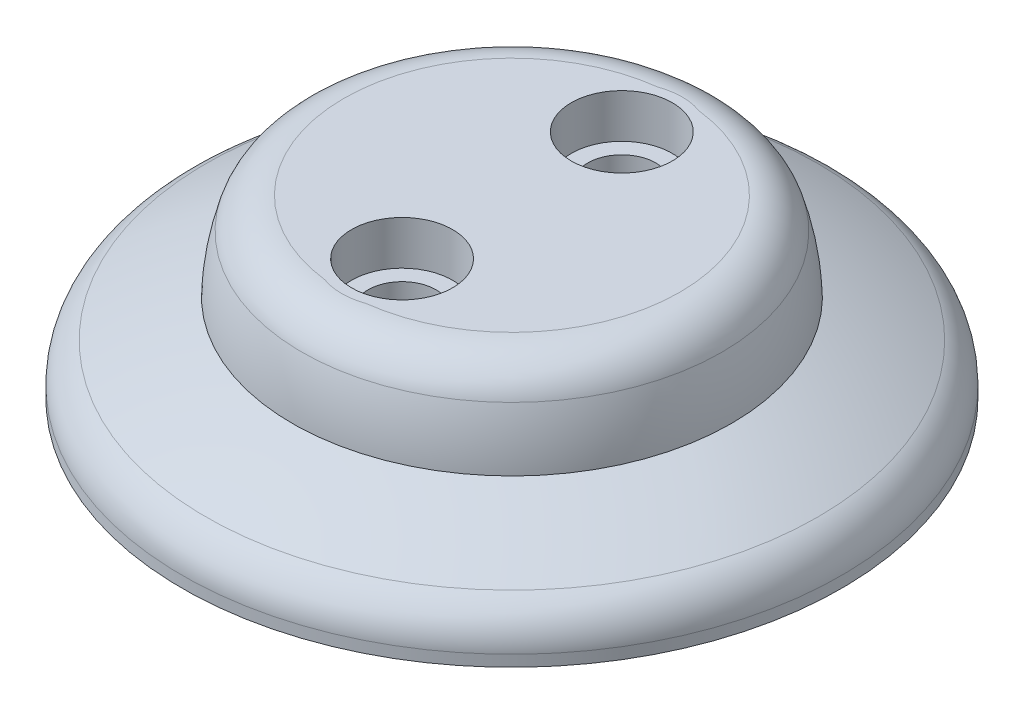
SolidWorks part; units mm, degrees
ref_plane "Alzado" through (0, 0, 0) normal (0, 0, 1) x (1, 0, 0)
ref_plane "Planta" through (0, 0, 0) normal (0, 1, 0) x (1, 0, 0)
ref_plane "Vista lateral" through (0, 0, 0) normal (1, 0, 0) x (0, 0, -1)
sketch "Croquis3" plane through (0, 0, 0) normal (0, 0, 1) x (1, 0, 0)
  line L0 (0, 0) -> (0, 8) construction
  line L1 (0, 8) -> (9, 8)
  line L2 (0, 0) -> (0, 8)
  line L3 (9.9936, 4) -> (0, 4) construction
  line L4 (0, 0) -> (15, 0)
  line L5 (15, 0) -> (15, 1.6942)
  arc A0 (9.9936, 4) -> (9, 8) centre (0, 3.6411) ccw
  arc A1 (15, 1.6942) -> (9.9936, 4) centre (0, -24.2865) ccw
  dimension "D3" = 20
  dimension "D4" = 60
  dimension "D1" = 8
  dimension "D2" = 9
  dimension "D6" = 4
  dimension "D7" = 15
revolve "Revolución1" add sketch "Croquis3" angle 360 about L2 region at (6.0585, 3.5686, 0)
sketch "Croquis4" plane through (0, 0, 0) normal (0, 0, 1) x (1, 0, 0)
  line L0 (0, 0.5) -> (0, 7.5)
  line L2 (0, 7.5) -> (0, 8) construction
  line L3 (9, 8) -> (-9, 8) construction
  line L8 (8.681, 7.5) -> (-8.681, 7.5)
  line L9 (-14.5, 0.5) -> (14.5, 0.5)
  line L10 (8.681, 7.5) -> (0, 7.5)
  line L11 (0, 0.5) -> (14.5, 0.5)
  line L12 (-14.5, 1.4039) -> (-14.5, 0.5)
  line L14 (14.5, 0.5) -> (14.5, 1.4039)
  line L15 (14.5, 0.5) -> (14.5, 1.4039)
  arc A8 (-9.5, 3.6419) -> (-14.5, 1.4039) centre (0, -24.2865) ccw
  arc A9 (-8.681, 7.5) -> (-9.5, 3.6419) centre (0, 3.6411) ccw
  arc A10 (14.5, 1.4039) -> (9.5, 3.6419) centre (0, -24.2865) ccw
  arc A11 (9.5, 3.6419) -> (8.681, 7.5) centre (0, 3.6411) ccw
  arc A14 (14.5, 1.4039) -> (9.5, 3.6419) centre (0, -24.2865) ccw
  arc A15 (9.5, 3.6419) -> (8.681, 7.5) centre (0, 3.6411) ccw
  dimension "D1" = 0.5
revolve "Cortar-Revolución1" cut sketch "Croquis4" angle 360 about L2
sketch "Croquis6" plane through (0, 0, 0) normal (0, -1, 0) x (1, 0, 0)
  circle A1 centre (0, 0) radius 14.5 construction
  circle A2 centre (0, 0) radius 14.5
extrude "Cortar-Extruir2" cut sketch "Croquis6" against normal blind 0.5
sketch "Croquis7" plane through (0, 7.5, 0) normal (0, -1, 0) x (1, 0, 0)
  line L0 (0, 0) -> (0, 8.681) construction
  line L1 (-8.681, 0) -> (8.681, 0) construction
  circle A0 centre (0, 0) radius 8.681 construction
  circle A1 centre (0, 5) radius 1.55
  circle A2 centre (0, 5) radius 2.05
  circle A3 centre (0, -5) radius 1.55
  circle A4 centre (0, -5) radius 2.05
  dimension "D1" = 3.1
  dimension "D3" = 0.5
  dimension "D2" = 5
extrude "Saliente-Extruir1" add sketch "Croquis7" along normal offset from surface (6.5 mm away) 1 up to face at (0, 0, -14.5)
sketch "Croquis8" plane through (0, 7.5, 0) normal (0, -1, 0) x (1, 0, 0)
  circle A0 centre (0, -5) radius 1.55 construction
  circle A1 centre (0, 5) radius 1.55 construction
  circle A2 centre (0, -5) radius 1.55
  circle A3 centre (0, 5) radius 1.55
extrude "Cortar-Extruir3" cut sketch "Croquis8" against normal blind 5.5
fillet "Redondeo1" radius 2 1 edges at (0, 8, -9)
fillet "Redondeo2" radius 2 1 edges at (0, 1.6942, -15)
sketch "Croquis9" plane through (0, 8, 0) normal (0, 1, 0) x (1, 0, 0)
  circle A0 centre (0, 5) radius 2.75
  circle A1 centre (0, -5) radius 2.75
  circle A2 centre (0, 5) radius 1.55 construction
  circle A3 centre (0, -5) radius 1.55 construction
  circle A4 centre (0, 5) radius 1.55
  circle A5 centre (0, -5) radius 1.55
  dimension "D1" = 5.5
extrude "Saliente-Extruir2" add sketch "Croquis9" against normal blind 3
fillet "Redondeo3" radius 1 2 edges at (0, 5, 7.05) (0, 5, -2.95)
sketch "Croquis10" plane through (0, 8, 0) normal (0, 1, 0) x (1, 0, 0)
  circle A0 centre (0, 5) radius 2.3
  circle A1 centre (0, -5) radius 2.3
  dimension "D1" = 4.6
extrude "Cortar-Extruir6" cut sketch "Croquis10" against normal blind 2
